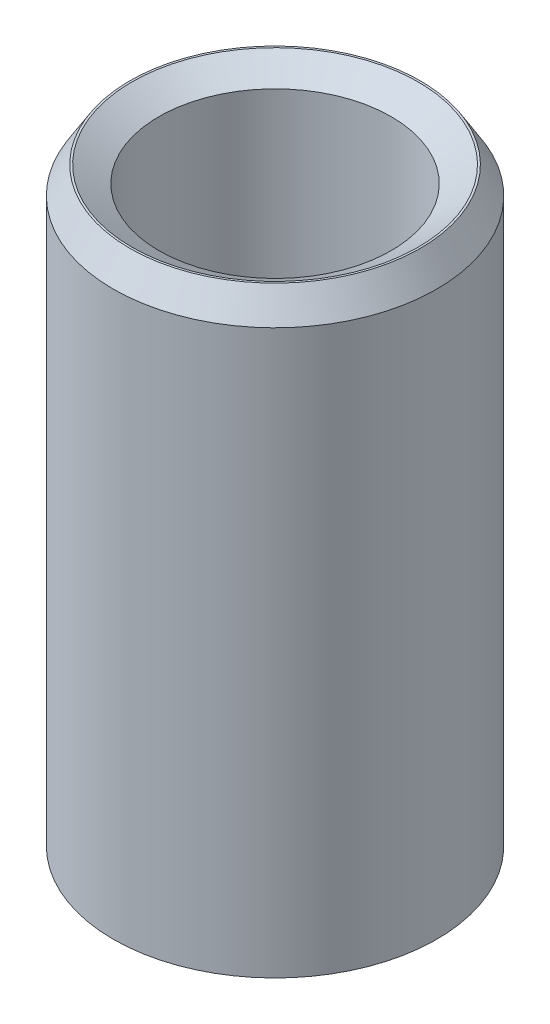
SolidWorks part; units mm, degrees
ref_plane "Front Plane" through (0, 0, 0) normal (0, 0, 1) x (1, 0, 0)
ref_plane "Top Plane" through (0, 0, 0) normal (0, 1, 0) x (1, 0, 0)
ref_plane "Right Plane" through (0, 0, 0) normal (1, 0, 0) x (0, 0, -1)
sketch "Sketch1" plane through (0, 0, 0) normal (0, 1, 0) x (1, 0, 0)
  circle A0 centre (0, 0) radius 15
  dimension "SLEEVE_OD" = 30
extrude "Boss-Extrude1" add sketch "Sketch1" along normal blind 56.2602
sketch "Sketch2" plane through (0, 0, 0) normal (0, 1, 0) x (1, 0, 0)
  circle A0 centre (0, 0) radius 10.7714
  dimension "BORE_D" = 21.5428
extrude "Cut-Extrude1" cut sketch "Sketch2" along normal through all
chamfer "Chamfer1" distance 2.5058 angle 31.443 4 edges at (0, 56.2602, 10.7714) (0, 0, 10.7714) (0, 0, 15) (0, 56.2602, 15) first distance on face at (0, 56.2602, 10.7714) first distance on face at (0, 0, 10.7714) first distance on face at (0, 56.2602, 15)
